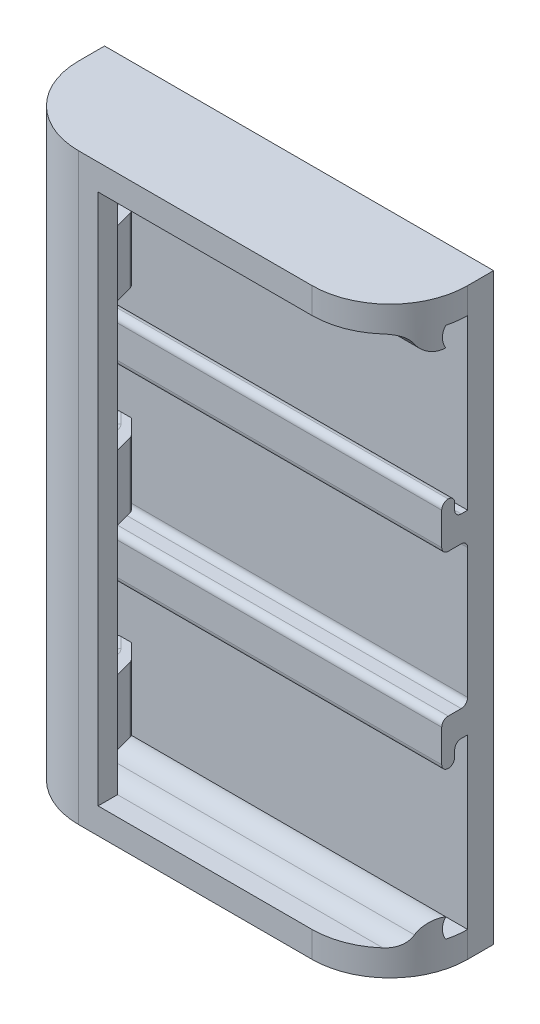
SolidWorks part; units mm, degrees
note: The reader was unsure of these and kept them because the rebuilt part matched: shared geometry of "Sketch2<3>", "Sketch2<4>".
ref_plane "Front Plane" through (0, 0, 0) normal (0, 0, 1) x (1, 0, 0)
ref_plane "Top Plane" through (0, 0, 0) normal (0, 1, 0) x (1, 0, 0)
ref_plane "Right Plane" through (0, 0, 0) normal (1, 0, 0) x (0, 0, -1)
sketch "Sketch1" plane through (0, 0, 0) normal (0, 0, 1) x (1, 0, 0)
  line L1 (-15, -22.5) -> (15, -22.5)
  line L2 (-15, -22.5) -> (-15, 22.5)
  line L3 (-15, 22.5) -> (15, 22.5)
  line L4 (15, -22.5) -> (15, 22.5)
  line L5 (-15, -22.5) -> (15, 22.5) construction
  line L6 (-15, 22.5) -> (15, -22.5) construction
  circle A0 centre (-10, 15) radius 2
  circle A1 centre (-10, 0) radius 2
  circle A2 centre (-10, -15) radius 2
  point P0 (0, 0)
  point P12 (0, 0)
  point P13 (0, 0)
  point P14 (0, 0)
  point P15 (-10.2935, -15.4403)
  point P16 (0, 0)
  dimension "D4" = 4
  dimension "D1" = 45
  dimension "D2" = 30
  dimension "D3" = 10
  dimension "D5" = 15
  dimension "D6" = 15
extrude "Boss-Extrude1" add sketch "Sketch1" along normal blind 2 contours L2 L3 L4 L1
sketch "Sketch2" plane through (0, 0, 0) normal (0, 1, 0) x (1, 0, 0)
  line L0 (-9, -8) -> (-9, -2)
  line L1 (-15, -2) -> (15, -2) construction
  line L2 (-15, -2) -> (-9, -2)
  line L3 (-9, -6.5) -> (-7.5, -6.5)
  line L4 (-9, -8) -> (-7.5, -8)
  line L5 (-9, -8) -> (-9, -2)
  line L6 (-9, -2) -> (-7.5, -2)
  line L7 (-7.5, -8) -> (-7.5, -2)
  arc A0 (-15, -2) -> (-9, -8) centre (-9, -2) ccw
  arc A1 (-13.5, -2) -> (-9, -6.5) centre (-9, -2) ccw
  dimension "D1" = 1.5
  dimension "D2" = 6
  dimension "D3" = 1.5
extrude "Boss-Extrude2" add sketch "Sketch2" along normal up to surface and the other way up to surface contours A1 L2 A0 L0 | L4 L7 L3 L0 up to face at (0, 22.5, 1) other way up to face at (0, -22.5, 1)
extrude "Boss-Extrude3" add sketch "Sketch2<3>" against normal blind 2 from surface at 22.5 contours L2 A1 L0 | A1 L2 A0 L0 | L3 L7 L6 L0 | L4 L7 L3 L0 starting at face at (-5.4083, 22.5, 4.1305)
sketch "Sketch2<3>" plane through (0, 0, 0) normal (0, 1, 0) x (1, 0, 0) same geometry as "Sketch2"
extrude "Boss-Extrude4" add sketch "Sketch2<4>" along normal blind 2 from surface at -22.5 contours A1 L2 A0 L0 | L2 A1 L0 | L3 L7 L6 L0 | L4 L7 L3 L0 starting at face at (-5.4083, -22.5, 4.1305)
sketch "Sketch2<4>" plane through (0, 0, 0) normal (0, 1, 0) x (1, 0, 0) same geometry as "Sketch2"
sketch "Sketch3" plane through (0, 0, 0) normal (1, 0, 0) x (0, 0, -1)
  line L0 (-8, 22.5) -> (-8, -22.5) construction
  line L1 (-2, 22.5) -> (-8, 22.5)
  line L2 (-2, 22.5) -> (-2, 20.5)
  line L3 (-2, 20.5) -> (-8, 20.5)
  line L4 (-8, 22.5) -> (-8, 20.5)
  line L5 (-6.5, 20.5) -> (-2, 20.5) construction
  line L6 (-2, 20.5) -> (-2, -20.5) construction
  line L7 (-2, 5.5) -> (-4, 5.5)
  line L8 (-2, 5.5) -> (-2, 7.5)
  line L9 (-2, 7.5) -> (-4, 7.5)
  line L10 (-4, 5.5) -> (-4, 7.5)
  line L12 (-4, 7.5) -> (-3, 7.5)
  line L13 (-4, 7.5) -> (-4, 9)
  line L14 (-4, 9) -> (-3, 9)
  line L15 (-3, 7.5) -> (-3, 9)
  arc A0 (-3.5, 20.5) -> (-3.5, 19) centre (-2.201, 19.75) ccw
  arc A1 (-3.5, 19) -> (-5.1875, 19.7262) centre (-3.875, 20.4524) cw
  arc A2 (-5.1875, 19.7262) -> (-6.5, 20.5) centre (-6.5, 19) ccw
  dimension "D1" = 1.5
  dimension "D5" = 1.5
  dimension "D4" = 1.5
  dimension "D2" = 1.5
  dimension "D3" = 1.5
  dimension "D6" = 2
  dimension "D7" = 1.5
  dimension "D8" = 7.5
  dimension "D9" = 2
  dimension "D10" = 1
extrude "Boss-Extrude5" add sketch "Sketch3" along normal up to surface and the other way up to body separate body contours L1 L4 L3 L2 | A2 A1 A0 L3 | L10 L7 L8 L9 | L9 L15 L14 L13 up to face at (15, 0, 1)
mirror "Mirror2" about plane through (0, 0, 0) normal (0, 1, 0) of "Boss-Extrude5"
fillet "Fillet1" radius 6 2 edges at (15, 21.5, 8) (15, -21.5, 8)
fillet "Fillet3" radius 0.5 10 edges at (0.8063, 7.5, 3) (0.8063, -7.5, 3) (0.75, -5.5, 2) (0.75, 5.5, 2) (0.9844, 5.5, 4) (0.9844, -5.5, 4) (0.8063, -9, 3) (0.8063, 9, 3) (0.9844, 9, 4) (0.9844, -9, 4)
sketch "Sketch4" plane through (0, 0, 0) normal (0, 1, 0) x (1, 0, 0)
  line L0 (-7.5, -6.5) -> (-7.5, -8)
  line L1 (-9, -8) -> (9, -8) construction
  line L2 (-9, -6.5) -> (-7.5, -6.5) construction
  line L4 (-11.5, -8) -> (-7.5, -8)
  line L5 (-9, -6.5) -> (-7.5, -6.5)
  line L6 (-11.5, -8) -> (-11.5, -6.5)
  line L7 (-9, -6.5) -> (-11.5, -6.5)
  arc A0 (-7.5, -6.5) -> (-10.875, -5.0476) centre (-9.5, -6.5) ccw
  arc A1 (-10.875, -5.0476) -> (-9, -6.5) centre (-10.5, -6.5) cw
  point P9 (-10.875, -6.5)
  point P13 (0, 0)
  point P15 (-11.2228, -6.5)
  point P16 (-11.3915, -8)
  point P17 (0, 0)
  point P18 (-11.1736, -6.5)
  dimension "D2" = 2
  dimension "D3" = 1.5
  dimension "D1" = 1.5
  dimension "D4" = 4
revolve "Revolve3" [suppressed] add sketch "Sketch4" angle 45 about L6
fillet "Fillet2" [suppressed] radius 0.5
pattern_linear "LPattern1" [suppressed] count 2 spacing 15 count 2 spacing 15
sketch "Sketch5" plane through (0, 0, 0) normal (0, 1, 0) x (1, 0, 0)
  line L0 (-7.5, -6.5) -> (-7.8882, -5.0511)
  line L1 (-7.8882, -5.0511) -> (-9.1382, -3.8011)
  line L2 (-9.1382, -3.8011) -> (-10.6382, -3.8011)
  line L3 (-10.6382, -3.8011) -> (-9.3882, -5.0511)
  line L4 (-9.3882, -5.0511) -> (-9, -6.5)
  line L5 (-9, -6.5) -> (-7.5, -6.5) construction
  line L6 (-9, -6.5) -> (-7.5, -6.5)
  dimension "D1" = 1.5
  dimension "D2" = 1.5
  dimension "D3" = 1.25
  dimension "D4" = 1.5
  dimension "D5" = 150
  dimension "D6" = 75
extrude "Boss-Extrude6" add sketch "Sketch5" along normal mid plane 5 contours L4 L6 L0 L1 L2 L3
fillet "Fillet4" radius 0.5 6 edges at (-10.0132, 2.5, 4.4261) (-10.0132, -2.5, 4.4261) (-9.1941, 2.5, 5.7756) (-9.1941, -2.5, 5.7756) (-9.3882, 0, 5.0511) (-7.8882, 0, 5.0511)
pattern_linear "LPattern2" count 2 spacing 15 along (0, 1, 0) count 2 spacing 15 along (0, -1, 0) of "Boss-Extrude6", "Fillet4"
